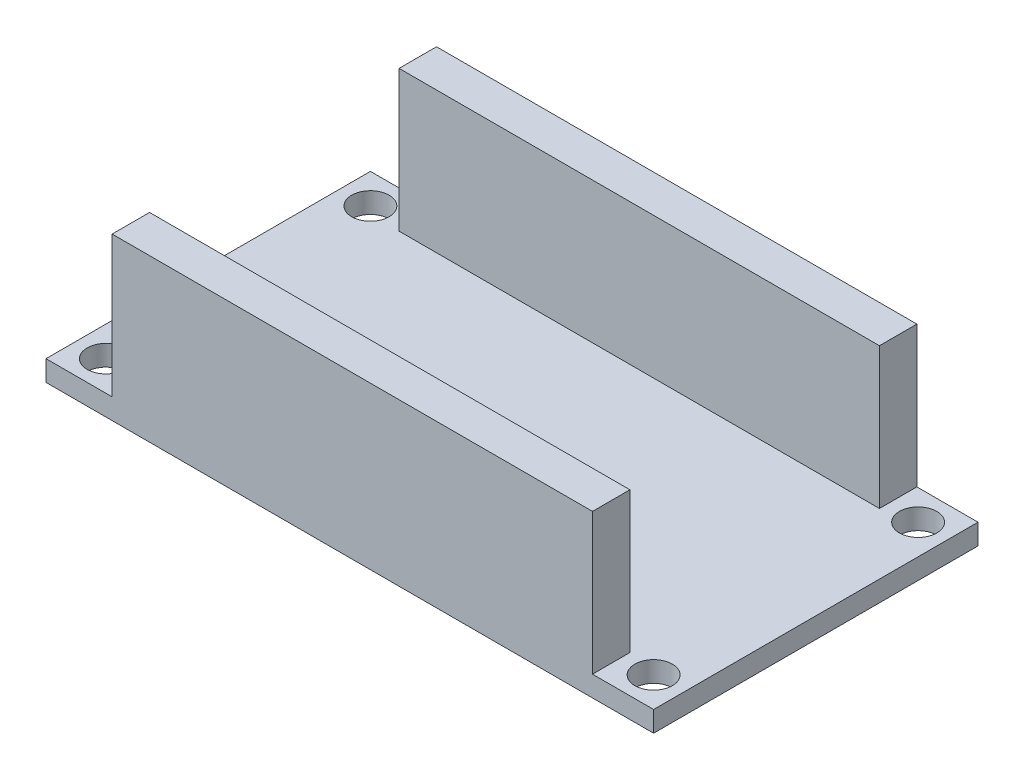
SolidWorks part; units mm, degrees
ref_plane "Front Plane" through (0, 0, 0) normal (0, 0, 1) x (1, 0, 0)
ref_plane "Top Plane" through (0, 0, 0) normal (0, 1, 0) x (1, 0, 0)
ref_plane "Right Plane" through (0, 0, 0) normal (1, 0, 0) x (0, 0, -1)
sketch "Sketch1" plane through (0, 0, 0) normal (0, 1, 0) x (1, 0, 0)
  line L0 (0, 0) -> (0, 6.7767) construction
  line L1 (-24.35, 13) -> (24.35, 13)
  line L2 (-24.35, 13) -> (-24.35, -13)
  line L3 (-24.35, -13) -> (24.35, -13)
  line L4 (24.35, 13) -> (24.35, -13)
  line L5 (-24.35, 13) -> (24.35, -13) construction
  line L6 (-24.35, -13) -> (24.35, 13) construction
  line L7 (0, 0) -> (9.7166, 0) construction
  circle A0 centre (-21.95, 10.6) radius 1.5
  circle A1 centre (-21.95, -10.6) radius 1.5
  circle A2 centre (21.95, -10.6) radius 1.5
  circle A3 centre (21.95, 10.6) radius 1.5
  point P0 (0, 0)
  dimension "D3" = 3
  dimension "D6" = 0.9
  dimension "D7" = 0.9
  dimension "D8" = 0.9
  dimension "D1" = 26
  dimension "D2" = 48.7
  dimension "D4" = 0.9
  dimension "D5" = 0.9
extrude "Boss-Extrude1" add sketch "Sketch1" along normal blind 1.65
sketch "Sketch2" plane through (0, 1.65, 0) normal (0, 1, 0) x (1, 0, 0)
  line L0 (24.35, 13) -> (-24.35, 13) construction
  line L1 (-19.05, 13) -> (19.45, 13)
  line L2 (-19.05, 13) -> (-19.05, 10)
  line L3 (-19.05, 10) -> (19.45, 10)
  line L4 (19.45, 13) -> (19.45, 10)
  line L5 (-24.35, 13) -> (-24.35, -13) construction
  line L6 (0, 0) -> (9.6057, 0) construction
  line L7 (19.45, -13) -> (19.45, -10)
  line L8 (-19.05, -13) -> (19.45, -13)
  line L9 (-19.05, -10) -> (19.45, -10)
  line L10 (-19.05, -13) -> (-19.05, -10)
  line L11 (-24.35, -13) -> (24.35, -13) construction
  dimension "D1" = 5.3
  dimension "D2" = 38.5
  dimension "D3" = 3
  dimension "D4" = 3
  dimension "D5" = 38.5
  dimension "D6" = 5.3
extrude "Boss-Extrude2" add sketch "Sketch2" along normal blind 11.3
